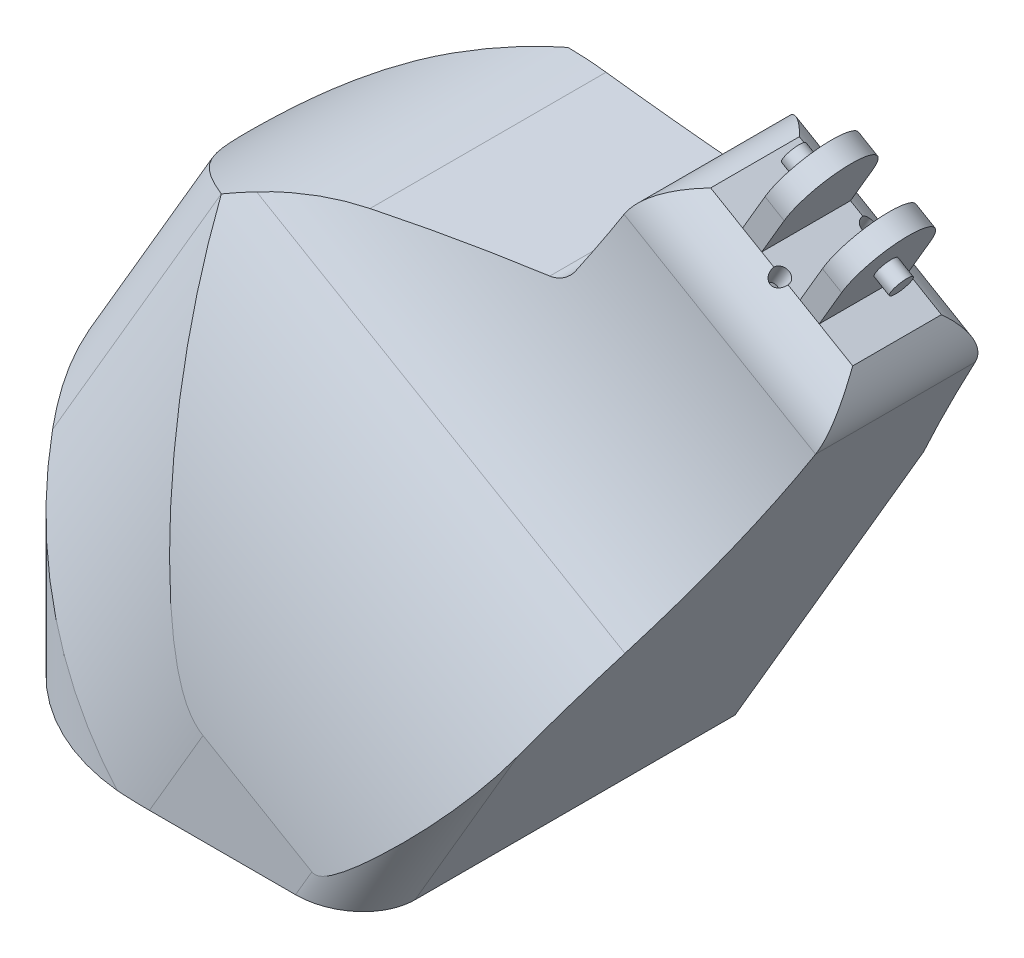
SolidWorks part; units mm, degrees
material "ABS"
ref_plane "Front Plane" through (0, 0, 0) normal (0, 0, 1) x (1, 0, 0)
ref_plane "Top Plane" through (0, 0, 0) normal (0, 1, 0) x (1, 0, 0)
ref_plane "Right Plane" through (0, 0, 0) normal (1, 0, 0) x (0, 0, -1)
sketch "Sketch1" plane through (0, 0, 0) normal (0, 0, 1) x (1, 0, 0)
  line L1 (0, 101.6) -> (101.6, 101.6)
  line L2 (0, 101.6) -> (0, 0)
  line L3 (0, 0) -> (101.6, 0)
  line L4 (101.6, 101.6) -> (101.6, 0)
  dimension "D1" = 101.6
extrude "Boss-Extrude1" add sketch "Sketch1" along normal blind 50.8
sketch "Sketch3" plane through (0, 0, 50.8) normal (0, 0, 1) x (1, 0, 0)
  line L0 (0, 0) -> (0, 20.32)
  line L1 (0, 0) -> (50.8, 0)
  line L2 (0, 0) -> (101.6, 0) construction
  line L5 (35.56, 55.88) -> (52.5466, 55.88)
  line L6 (54.8304, 57.1898) -> (58.8347, 64.0343)
  line L22 (50.8, 0) -> (80.7584, 51.2082)
  line L25 (78.2054, 60.96) -> (68.5865, 66.5874)
  arc A0 (0, 20.32) -> (35.56, 55.88) centre (35.56, 20.32) cw
  arc A1 (52.5466, 55.88) -> (54.8304, 57.1898) centre (52.5466, 58.526) ccw
  arc A2 (58.8347, 64.0343) -> (68.5865, 66.5874) centre (64.9871, 60.435) cw
  arc A3 (80.7584, 51.2082) -> (78.2054, 60.96) centre (74.606, 54.8076) ccw
  point P10 (56.8326, 60.6121)
  dimension "D1" = 60.96
  dimension "D3" = 55.88
  dimension "D4" = 20.32
  dimension "D5" = 25.4
  dimension "D8" = 50.8
extrude "Cut-Extrude1" cut sketch "Sketch3" against normal blind 69.342 flip side to cut
sketch "Sketch4" plane through (37.8466, -22.1414, 0) normal (0.8631, -0.505, 0) x (0, 0, -1)
  line L0 (0, 25.6522) -> (0, 123.9372)
  line L1 (0, 123.9372) -> (-50.8, 123.9372)
  line L2 (-50.8, 123.9372) -> (-50.8, 25.6522)
  line L4 (-14.3487, 90.9787) -> (-24.5087, 90.9787)
  line L6 (0, 84.98) -> (-50.8, 84.98) construction
  line L7 (0, 25.6522) -> (-50.8, 25.6522) construction
  line L8 (-50.8, 25.6522) -> (-50.8, 84.98) construction
  arc A1 (-28.5606, 84.98) -> (-24.5087, 90.9787) centre (-20.7316, 84.0596) cw
  arc A3 (-10.2836, 84.98) -> (-14.3487, 90.9787) centre (-17.8078, 84.2578) ccw
  arc A4 (-28.5606, 84.98) -> (-37.9355, 60.33) centre (-82.2515, 91.2921) cw
  arc A5 (-37.9355, 60.33) -> (-50.8, 25.6522) centre (22.2578, 18.2749) ccw
  arc A6 (-10.2836, 84.98) -> (-4.4444, 54.8125) centre (150.0904, 100.373) ccw
  arc A7 (-4.4444, 54.8125) -> (0, 25.6522) centre (-109.2043, 23.9268) cw
  dimension "D2" = 98.285
extrude "Cut-Extrude2" cut sketch "Sketch4" against normal blind 69.342
sketch "Sketch5" plane through (0, 0, 0) normal (0, -1, 0) x (1, 0, 0)
  line L0 (50.8, 50.8) -> (50.8, 86.9289)
  line L1 (50.8, 86.9289) -> (-27.7774, 86.9289)
  line L2 (-27.7774, 86.9289) -> (-27.7774, 0)
  line L3 (-27.7774, 0) -> (25.4, 0)
  line L4 (0, 0) -> (50.8, 0) construction
  line L5 (50.8, 50.8) -> (25.4, 50.8)
  line L6 (1.0955, 50.8) -> (50.8, 50.8) construction
  line L7 (0, 50.8) -> (0, 0) construction
  arc A0 (25.4, 50.8) -> (25.4, 0) centre (25.4, 25.4) ccw
  point P10 (0, 0)
ref_plane "Plane4" through (12.9534, 22.1414, 0) normal (-0.505, -0.8631, 0) x (-0.8631, 0.505, 0)
extrude "Cut-Extrude18" cut sketch "Sketch5" against normal blind 127
sketch "Sketch13" plane through (12.9534, 22.1414, 0) normal (-0.505, -0.8631, 0) x (-0.8631, 0.505, 0)
  line L0 (-23.0707, -50.8) -> (-37.508, -50.8)
  line L1 (-14.4201, -50.8) -> (-43.8475, -50.8) construction
  line L2 (-43.8475, 0) -> (-43.8475, -50.8) construction
  line L3 (-43.8475, -44.4605) -> (-43.8475, -7.817)
  arc A0 (-37.508, -50.8) -> (-43.8475, -44.4605) centre (-37.508, -44.4605) cw
  arc A1 (-23.0707, -50.8) -> (6.8839, -39.3198) centre (-23.0707, -5.9807) ccw
  arc A2 (6.8839, -39.3198) -> (7.645, -11.6425) centre (-5.8745, -25.1198) ccw
  arc A3 (7.645, -11.6425) -> (-20.4006, 0) centre (-20.4006, -39.6008) ccw
  arc A4 (-20.4006, 0) -> (-43.8475, -7.817) centre (-20.4006, -39.0726) ccw
extrude "Cut-Extrude17" cut sketch "Sketch13" against normal blind 127 and the other way blind 127 flip side to cut
shell "Shell12" thickness 2.54 removed face at (32.9722, 0, 33.8886)
sketch "Sketch7" plane through (45.941, 78.5273, 0) normal (0.505, 0.8631, 0) x (0.8631, -0.505, 0)
  line L0 (25.9666, -14.3487) -> (25.9666, -24.5087)
  line L1 (25.9666, -14.3487) -> (28.5066, -14.3487)
  line L2 (25.9666, -24.5087) -> (28.5066, -24.5087)
  line L3 (28.5066, -14.3487) -> (28.5066, -24.5087)
  line L4 (21.7253, -14.3487) -> (40.5697, -14.3487) construction
  line L5 (21.7253, -24.5087) -> (40.5697, -24.5087) construction
  line L6 (33.5866, -14.3487) -> (36.1266, -14.3487)
  line L7 (33.5866, -14.3487) -> (33.5866, -24.5087)
  line L8 (36.1266, -14.3487) -> (36.1266, -24.5087)
  line L9 (33.5866, -24.5087) -> (36.1266, -24.5087)
  dimension "D1" = 2.54
  dimension "D2" = 5.08
extrude "Boss-Extrude2" add sketch "Sketch7" along normal blind 10.16
sketch "Sketch8" plane through (22.4128, -13.1122, 0) normal (-0.8631, 0.505, 0) x (0, 0, 1)
  circle A0 centre (19.4287, 95.9798) radius 1.27
  dimension "D1" = 2.54
  dimension "D2" = 5.08
  dimension "D3" = 5.1588
extrude "Boss-Extrude3" add sketch "Sketch8" along normal blind 2.032
sketch "Sketch9" plane through (31.1823, -18.2427, 0) normal (0.8631, -0.505, 0) x (0, 0, -1)
  line L0 (-24.5087, 101.1387) -> (-14.3487, 101.1387) construction
  line L1 (-14.3487, 101.1387) -> (-14.3487, 90.9787) construction
  circle A0 centre (-19.4287, 96.0587) radius 1.2398
  dimension "D1" = 2.4796
  dimension "D2" = 5.08
  dimension "D3" = 5.08
extrude "Boss-Extrude4" add sketch "Sketch9" along normal blind 2.032
sketch "Sketch10" plane through (31.1823, -18.2427, 0) normal (0.8631, -0.505, 0) x (0, 0, -1)
  line L0 (-24.5087, 96.0587) -> (-24.5087, 108.7409)
  line L1 (-24.5087, 101.1387) -> (-24.5087, 90.9787) construction
  line L2 (-14.3487, 96.0587) -> (-14.3487, 108.7409)
  line L3 (-14.3487, 101.1387) -> (-14.3487, 90.9787) construction
  line L4 (-14.3487, 108.7409) -> (-24.5087, 108.7409)
  arc A0 (-24.5087, 96.0587) -> (-14.3487, 96.0587) centre (-19.4287, 96.0587) cw
extrude "Cut-Extrude14" cut sketch "Sketch10" against normal blind 14.986
sketch "Sketch12" plane through (45.941, 78.5273, 0) normal (0.505, 0.8631, 0) x (0.8631, -0.505, 0)
  line L0 (28.5066, -14.3487) -> (33.5866, -14.3487) construction
  line L1 (28.5066, -24.5087) -> (33.5866, -24.5087) construction
  circle A0 centre (31.0466, -14.3487) radius 0.8983
  circle A1 centre (31.0466, -24.5087) radius 0.9342
extrude "Cut-Extrude16" cut sketch "Sketch12" against normal blind 14.986
